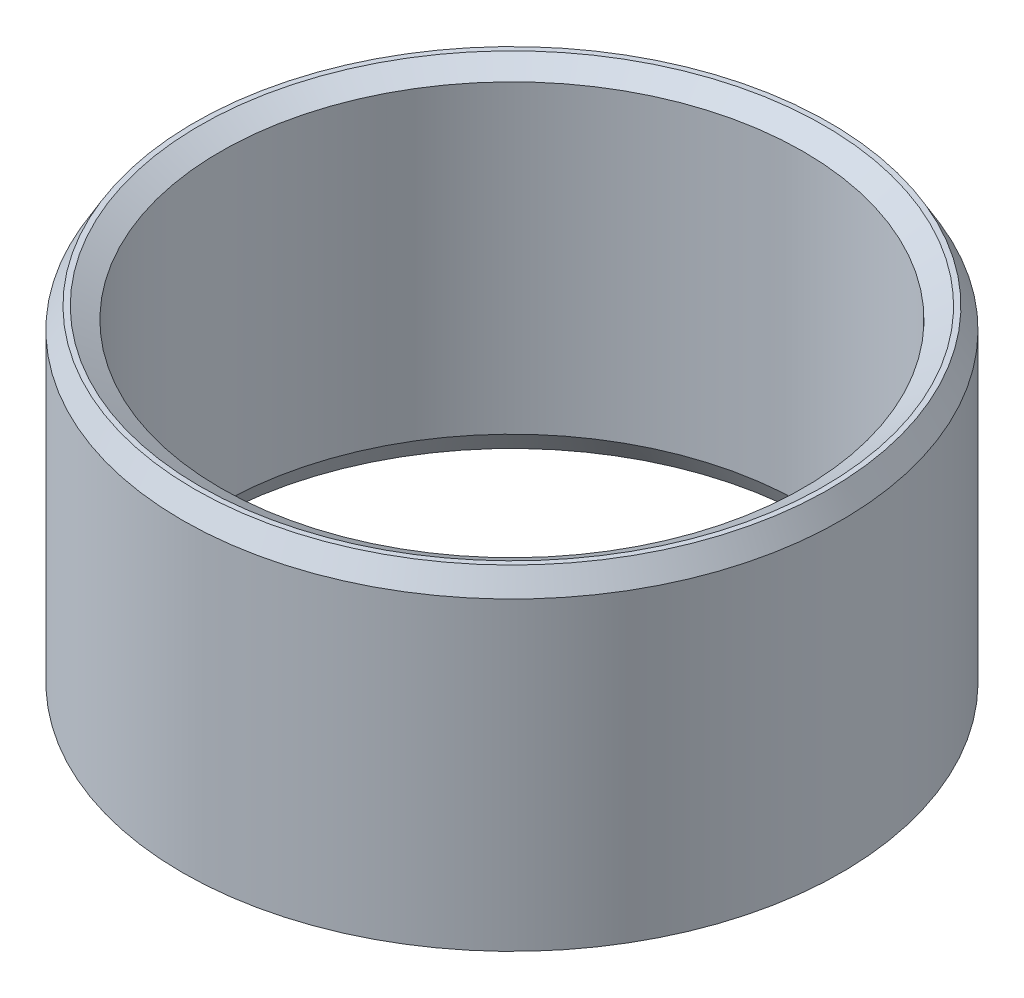
SolidWorks part; units mm, degrees
ref_plane "Front Plane" through (0, 0, 0) normal (0, 0, 1) x (1, 0, 0)
ref_plane "Top Plane" through (0, 0, 0) normal (0, 1, 0) x (1, 0, 0)
ref_plane "Right Plane" through (0, 0, 0) normal (1, 0, 0) x (0, 0, -1)
sketch "Sketch1" plane through (0, 0, 0) normal (0, 1, 0) x (1, 0, 0)
  circle A0 centre (0, 0) radius 37.5
  dimension "SLEEVE_OD" = 75
extrude "Boss-Extrude1" add sketch "Sketch1" along normal blind 38.4735
sketch "Sketch2" plane through (0, 0, 0) normal (0, 1, 0) x (1, 0, 0)
  circle A0 centre (0, 0) radius 33.1559
  dimension "BORE_D" = 66.3118
extrude "Cut-Extrude1" cut sketch "Sketch2" along normal through all
chamfer "Chamfer1" distance 2.3799 angle 30 4 edges at (0, 38.4735, 33.1559) (0, 0, 33.1559) (0, 0, 37.5) (0, 38.4735, 37.5) first distance on face at (0, 38.4735, 33.1559) first distance on face at (0, 0, 33.1559) first distance on face at (0, 38.4735, 37.5)
